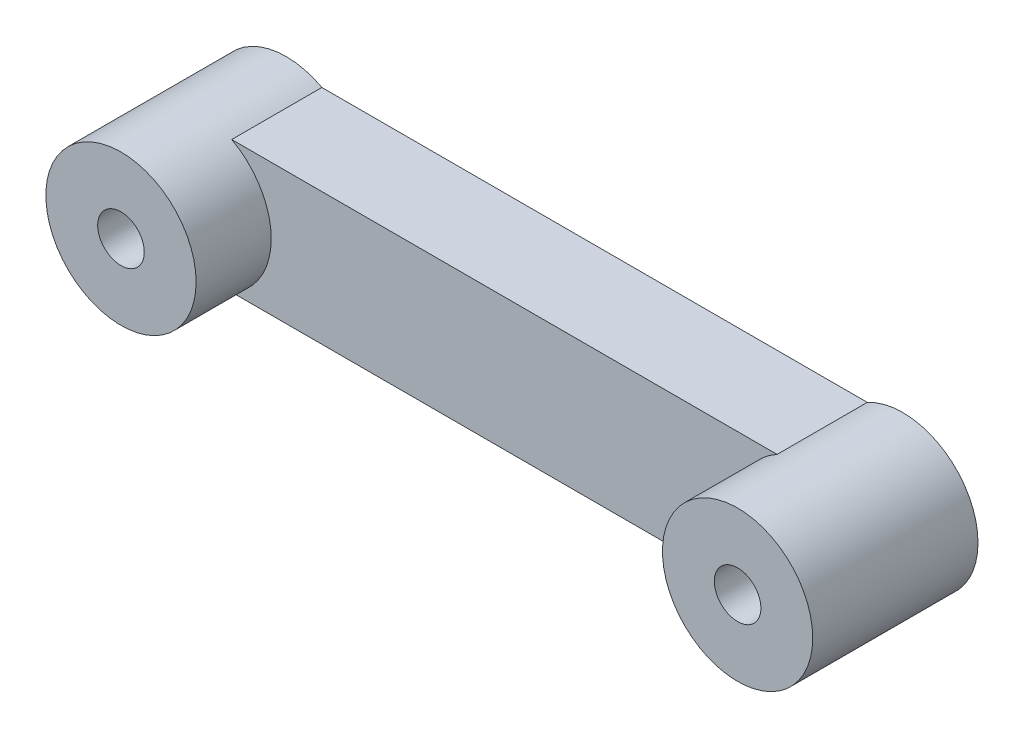
SolidWorks part; units mm, degrees
ref_plane "Plan de face" through (0, 0, 0) normal (0, 0, 1) x (1, 0, 0)
ref_plane "Plan de dessus" through (0, 0, 0) normal (0, 1, 0) x (1, 0, 0)
ref_plane "Plan de droite" through (0, 0, 0) normal (1, 0, 0) x (0, 0, -1)
sketch "Esquisse1" plane through (0, 0, 0) normal (0, 0, 1) x (1, 0, 0)
  line L0 (2.3705, 4.4023) -> (38.6705, 4.4023)
  line L1 (14.9398, 0) -> (50014.9398, 0) construction
  line L2 (2.3705, -4.4023) -> (38.6705, -4.4023)
  arc A1 (2.3705, 4.4023) -> (2.3705, -4.4023) centre (0, 0) ccw
  arc A2 (38.6705, -4.4023) -> (38.6705, 4.4023) centre (41.0411, 0) ccw
  dimension "D1" = 10
  dimension "D2" = 10
  dimension "D3" = 36.3
extrude "Boss.-Extru.1" add sketch "Esquisse1" along normal blind 3 and the other way blind 3
sketch "Esquisse2" plane through (0, 0, 3) normal (0, 0, 1) x (1, 0, 0)
  line L0 (0, 0) -> (50000, 0) construction
  circle A0 centre (0, 0) radius 1.55
  circle A2 centre (41.0411, 0) radius 1.55
  arc A3 (38.6705, -4.4023) -> (38.6705, 4.4023) centre (41.0411, 0) ccw construction
  dimension "D1" = 3.1
  dimension "D2" = 3.1
extrude "Enlèv. mat.-Extru.1" cut sketch "Esquisse2" along direction (0, 0, 1) on the side against the normal up to surface (6 mm away) contours A0 | A2 L0 | L0 A2 | L0 A0 region at (41.0411, 0.6578, 3) region at (41.0411, -0.6578, 3) region at (-1.5062, 0, 3) up to face at (20.5205, 0, -3)
sketch "Sketch1" plane through (0, 0, 3) normal (0, 0, 1) x (1, 0, 0)
  circle A0 centre (0, 0) radius 5
  circle A1 centre (0, 0) radius 1.55
  circle A2 centre (41.0411, 0) radius 1.55
  circle A3 centre (41.0411, 0) radius 5
  arc A6 (38.6705, -4.4023) -> (38.6705, 4.4023) centre (41.0411, 0) ccw construction
  arc A7 (2.3705, 4.4023) -> (2.3705, -4.4023) centre (0, 0) ccw construction
extrude "Boss-Extrude1" add sketch "Sketch1" along normal blind 5
